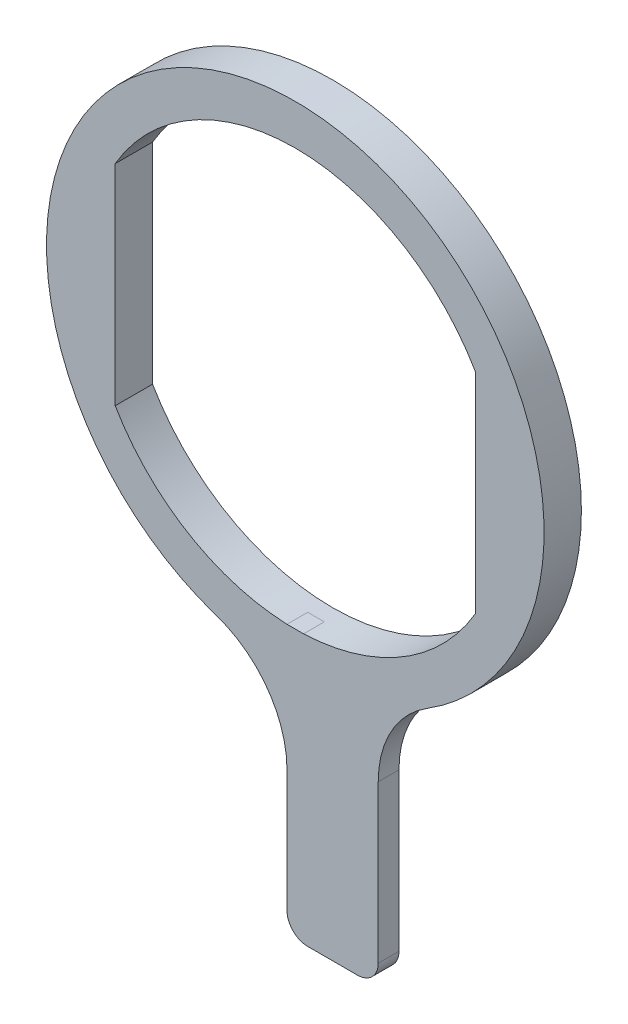
SolidWorks part; units mm, degrees
material "PET"
ref_plane "Ebene vorne" through (0, 0, 0) normal (0, 0, 1) x (1, 0, 0)
ref_plane "Ebene oben" through (0, 0, 0) normal (0, 1, 0) x (1, 0, 0)
ref_plane "Ebene rechts" through (0, 0, 0) normal (1, 0, 0) x (0, 0, -1)
sketch "Skizze1" plane through (0, 0, 0) normal (0, 0, 1) x (1, 0, 0)
  line L0 (8.6853, 5.0566) -> (8.6853, -5.0566)
  line L1 (-8.6603, 5) -> (8.6603, 5) construction
  line L2 (-8.6603, 5) -> (-8.6603, -5) construction
  line L3 (-8.6603, -5) -> (8.6603, -5) construction
  line L4 (8.6603, 5) -> (8.6603, -5) construction
  line L5 (-8.6853, 5.0566) -> (-8.6853, -5.0566)
  circle A0 centre (0, 0) radius 10 construction
  circle A1 centre (0, 0) radius 12
  circle A2 centre (0, 0) radius 10.05
  dimension "D1" = 20
  dimension "D2" = 24
  dimension "D3" = 10
  dimension "D4" = 20.1
  dimension "D5" = 0.05
  dimension "D6" = 0.05
extrude "Aufsatz-Linear austragen1" add sketch "Skizze1" along normal blind 1.8 contours A1 A2 region at (-11.6606, 0, 0)
sketch "Skizze2" plane through (0, 0, 1.8) normal (0, 0, 1) x (1, 0, 0)
  line L0 (0, 0) -> (0, -23) construction
  line L1 (-0.4, -10.042) -> (4, -10.042)
  line L2 (-0.4, -10.042) -> (-0.4, -23)
  line L3 (-0.4, -23) -> (4, -23)
  line L4 (4, -10.042) -> (4, -23)
  circle A0 centre (0, 0) radius 10.05 construction
  dimension "D1" = 0.4
  dimension "D2" = 4
  dimension "D3" = 23
extrude "Aufsatz-Linear austragen2" add sketch "Skizze2" against normal blind 1
fillet "Verrundung1" radius 5 2 edges at (4, -11.3137, 1.3) (-0.4, -11.9933, 1.3)
fillet "Verrundung2" radius 1 2 edges at (4, -23, 1.3) (-0.4, -23, 1.3)
extrude "Aufsatz-Linear austragen3" add sketch "Skizze1<3>" along normal up to surface (1.8 mm away) contours L5 A2 | L0 A2 region at (9.2345, 0, 0) region at (-9.2345, 0, 0) up to face at (1.3602, -14.8704, 1.8)
sketch "Skizze1<3>" plane through (0, 0, 0) normal (0, 0, 1) x (1, 0, 0) same geometry as "Skizze1"
